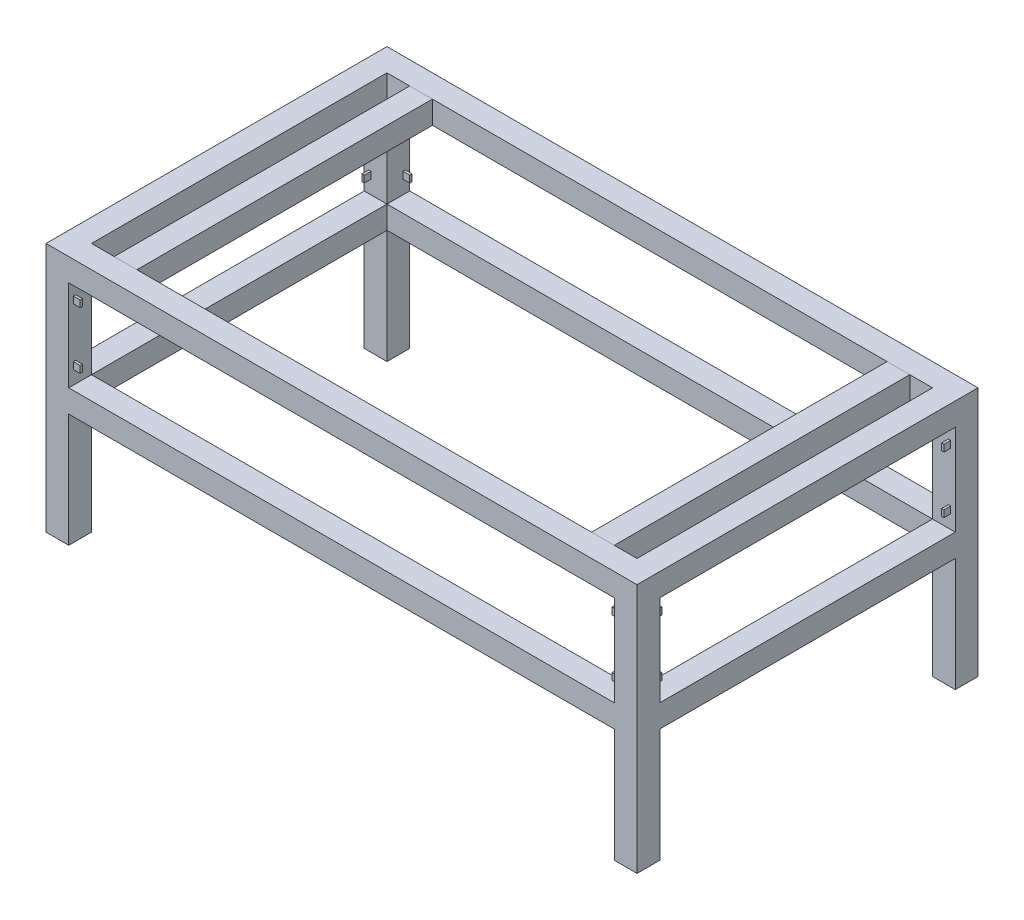
SolidWorks part; units mm, degrees
ref_plane "Plan de face" through (0, 0, 0) normal (0, 0, 1) x (1, 0, 0)
ref_plane "Plan de dessus" through (0, 0, 0) normal (0, 1, 0) x (1, 0, 0)
ref_plane "Plan de droite" through (0, 0, 0) normal (1, 0, 0) x (0, 0, -1)
sketch "Esquisse1" plane through (0, 0, 0) normal (0, 1, 0) x (1, 0, 0)
  line L1 (0, 0) -> (1300, 0)
  line L2 (0, 0) -> (0, 750)
  line L3 (0, 750) -> (1300, 750)
  line L4 (1300, 0) -> (1300, 750)
  line L5 (50, 700) -> (1250, 700)
  line L6 (50, 700) -> (50, 50)
  line L7 (50, 50) -> (1250, 50)
  line L8 (1250, 700) -> (1250, 50)
  dimension "D1" = 1300
  dimension "D2" = 750
  dimension "D3" = 50
  dimension "D4" = 50
  dimension "D5" = 50
  dimension "D6" = 50
extrude "Boss.-Extru.1" add sketch "Esquisse1" against normal blind 550
sketch "Esquisse2" plane through (0, 0, 0) normal (0, 0, 1) x (1, 0, 0)
  line L0 (0, 0) -> (1300, 0) construction
  line L1 (50, -50) -> (1250, -50)
  line L2 (50, -50) -> (50, -250)
  line L3 (50, -250) -> (1250, -250)
  line L4 (1250, -50) -> (1250, -250)
  line L5 (50, -300) -> (1250, -300)
  line L6 (50, -300) -> (50, -550)
  line L7 (50, -550) -> (1250, -550)
  line L8 (1250, -300) -> (1250, -550)
  line L9 (0, -550) -> (1300, -550) construction
  line L10 (1300, -550) -> (1300, 0) construction
  line L11 (0, -550) -> (0, 0) construction
  point P12 (1250, -425)
  dimension "D1" = 50
  dimension "D2" = 50
  dimension "D3" = 200
  dimension "D4" = 0
  dimension "D5" = 50
  dimension "D6" = 50
  dimension "D7" = 50
  dimension "D8" = 50
extrude "Enlèv. mat.-Extru.1" cut sketch "Esquisse2" against normal through all
sketch "Esquisse3" plane through (0, 0, 0) normal (-1, 0, 0) x (0, 0, 1)
  line L0 (-750, -550) -> (0, -550) construction
  line L1 (-700, -50) -> (-50, -50)
  line L2 (-700, -50) -> (-700, -250)
  line L3 (-700, -250) -> (-50, -250)
  line L4 (-50, -50) -> (-50, -250)
  line L5 (-700, -300) -> (-50, -300)
  line L6 (-700, -300) -> (-700, -550)
  line L7 (-700, -550) -> (-50, -550)
  line L8 (-50, -300) -> (-50, -550)
  line L9 (-750, 0) -> (0, 0) construction
  line L10 (0, -550) -> (0, 0) construction
  line L11 (-750, -550) -> (-750, 0) construction
  dimension "D1" = 50
  dimension "D2" = 50
  dimension "D3" = 50
  dimension "D4" = 50
  dimension "D5" = 50
  dimension "D6" = 200
  dimension "D7" = 50
extrude "Enlèv. mat.-Extru.2" cut sketch "Esquisse3" against normal through all
sketch "Esquisse4" plane through (0, 0, 0) normal (0, 1, 0) x (1, 0, 0)
  line L0 (1250, 700) -> (50, 700) construction
  line L1 (100, 700) -> (150, 700)
  line L2 (100, 700) -> (100, 50)
  line L3 (100, 50) -> (150, 50)
  line L4 (150, 700) -> (150, 50)
  line L5 (50, 50) -> (1250, 50) construction
  line L6 (50, 700) -> (50, 50) construction
  line L7 (1150, 700) -> (1200, 700)
  line L8 (1150, 700) -> (1150, 50)
  line L9 (1150, 50) -> (1200, 50)
  line L10 (1200, 700) -> (1200, 50)
  line L11 (1250, 50) -> (1250, 700) construction
  dimension "D1" = 50
  dimension "D2" = 50
  dimension "D3" = 50
  dimension "D4" = 50
extrude "Boss.-Extru.2" add sketch "Esquisse4" against normal blind 50 separate body
sketch "Esquisse5" plane through (1250, 0, 0) normal (-1, 0, 0) x (0, 0, 1)
  line L0 (-750, -250) -> (-750, -50) construction
  line L1 (-750, -80) -> (-735, -80)
  line L2 (-750, -80) -> (-750, -95)
  line L3 (-750, -95) -> (-735, -95)
  line L4 (-735, -80) -> (-735, -95)
  line L5 (-740, -80) -> (-740, -95)
  line L6 (-750, -205) -> (-735, -205)
  line L7 (-750, -205) -> (-750, -220)
  line L8 (-750, -220) -> (-735, -220)
  line L9 (-735, -205) -> (-735, -220)
  line L10 (-740, -205) -> (-740, -220)
  line L11 (-750, -50) -> (-700, -50) construction
  line L12 (-750, -250) -> (-700, -250) construction
  dimension "D1" = 10
  dimension "D2" = 5
  dimension "D3" = 5
  dimension "D4" = 15
  dimension "D5" = 15
  dimension "D6" = 30
  dimension "D7" = 30
extrude "Boss.-Extru.3" add sketch "Esquisse5" along normal blind 15 contours L1 L5 L3 L4 | L6 L10 L8 L9 region at (1250, -87.5, -737.5) region at (1250, -212.5, -737.5)
sketch "Esquisse6" plane through (0, 0, -700) normal (0, 0, 1) x (1, 0, 0)
  line L0 (1300, -50) -> (1300, -250) construction
  line L1 (1300, -80) -> (1285, -80)
  line L2 (1300, -80) -> (1300, -95)
  line L3 (1300, -95) -> (1285, -95)
  line L4 (1285, -80) -> (1285, -95)
  line L5 (1290, -80) -> (1290, -95)
  line L6 (1300, -220) -> (1285, -220)
  line L7 (1300, -220) -> (1300, -205)
  line L8 (1300, -205) -> (1285, -205)
  line L9 (1285, -220) -> (1285, -205)
  line L10 (1290, -205) -> (1290, -220)
  line L11 (1300, -50) -> (1250, -50) construction
  line L12 (1300, -250) -> (1250, -250) construction
  point P18 (1292.5, -220)
  dimension "D1" = 15
  dimension "D2" = 15
  dimension "D3" = 5
  dimension "D4" = 5
  dimension "D5" = 10
  dimension "D6" = 30
  dimension "D7" = 30
extrude "Boss.-Extru.4" add sketch "Esquisse6" along normal blind 15 contours L5 L1 L4 L3 | L10 L8 L9 L6 region at (1287.5, -87.5, -700) region at (1287.5, -212.5, -700)
sketch "Esquisse7" plane through (50, 0, 0) normal (1, 0, 0) x (0, 0, -1)
  line L0 (750, -50) -> (750, -250) construction
  line L1 (750, -80) -> (735, -80)
  line L2 (750, -80) -> (750, -95)
  line L3 (750, -95) -> (735, -95)
  line L4 (735, -80) -> (735, -95)
  line L5 (740, -80) -> (740, -95)
  line L6 (750, -220) -> (735, -220)
  line L7 (750, -220) -> (750, -205)
  line L8 (750, -205) -> (735, -205)
  line L9 (735, -220) -> (735, -205)
  line L10 (740, -205) -> (740, -220)
  line L11 (750, -250) -> (700, -250) construction
  line L12 (750, -50) -> (700, -50) construction
  dimension "D1" = 15
  dimension "D2" = 15
  dimension "D3" = 10
  dimension "D4" = 5
  dimension "D5" = 5
  dimension "D6" = 30
  dimension "D7" = 30
extrude "Boss.-Extru.5" add sketch "Esquisse7" along normal blind 15 contours L5 L1 L4 L3 | L10 L8 L9 L6 region at (50, -87.5, -737.5) region at (50, -212.5, -737.5)
sketch "Esquisse8" plane through (0, 0, -700) normal (0, 0, 1) x (1, 0, 0)
  line L0 (0, -50) -> (0, -250) construction
  line L1 (10, -80) -> (10, -95)
  line L2 (0, -80) -> (15, -80)
  line L3 (0, -80) -> (0, -95)
  line L4 (0, -95) -> (15, -95)
  line L5 (15, -80) -> (15, -95)
  line L6 (0, -205) -> (15, -205)
  line L7 (0, -205) -> (0, -220)
  line L8 (0, -220) -> (15, -220)
  line L9 (15, -205) -> (15, -220)
  line L10 (10, -205) -> (10, -220)
  line L11 (50, -250) -> (0, -250) construction
  line L13 (50, -50) -> (0, -50) construction
  point P16 (7.5, -220)
  dimension "D1" = 15
  dimension "D2" = 5
  dimension "D3" = 10
  dimension "D4" = 30
  dimension "D5" = 5
  dimension "D6" = 10
  dimension "D7" = 15
  dimension "D8" = 30
extrude "Boss.-Extru.6" add sketch "Esquisse8" along normal blind 15 contours L5 L2 L1 L4 | L6 L10 L8 L9 region at (12.5, -87.5, -700) region at (12.5, -212.5, -700)
sketch "Esquisse10" plane through (50, 0, 0) normal (1, 0, 0) x (0, 0, -1)
  line L0 (0, -50) -> (0, -250) construction
  line L1 (0, -80) -> (15, -80)
  line L2 (0, -80) -> (0, -95)
  line L3 (0, -95) -> (15, -95)
  line L4 (15, -80) -> (15, -95)
  line L5 (10, -80) -> (10, -95)
  line L6 (0, -205) -> (15, -205)
  line L7 (0, -205) -> (0, -220)
  line L8 (0, -220) -> (15, -220)
  line L9 (15, -205) -> (15, -220)
  line L10 (10, -205) -> (10, -220)
  line L11 (50, -250) -> (0, -250) construction
  line L12 (50, -50) -> (0, -50) construction
  point P18 (7.5, -80)
  dimension "D1" = 5
  dimension "D2" = 5
  dimension "D3" = 15
  dimension "D4" = 15
  dimension "D5" = 15
  dimension "D6" = 15
  dimension "D7" = 30
  dimension "D8" = 30
extrude "Boss.-Extru.7" add sketch "Esquisse10" along normal blind 15 contours L1 L5 L3 L4 | L6 L10 L8 L9 region at (50, -87.5, -12.5) region at (50, -212.5, -12.5)
sketch "Esquisse12" plane through (0, 0, -50) normal (0, 0, -1) x (-1, 0, 0)
  line L0 (0, -250) -> (0, -50) construction
  line L1 (0, -80) -> (-15, -80)
  line L2 (0, -80) -> (0, -95)
  line L3 (0, -95) -> (-15, -95)
  line L4 (-15, -80) -> (-15, -95)
  line L5 (-10, -80) -> (-10, -95)
  line L6 (0, -205) -> (-15, -205)
  line L7 (0, -205) -> (0, -220)
  line L8 (0, -220) -> (-15, -220)
  line L9 (-15, -205) -> (-15, -220)
  line L10 (-10, -205) -> (-10, -220)
  line L11 (-50, -50) -> (0, -50) construction
  line L12 (-50, -250) -> (0, -250) construction
  point P14 (-15, -87.5)
  dimension "D1" = 15
  dimension "D2" = 15
  dimension "D3" = 15
  dimension "D4" = 15
  dimension "D5" = 5
  dimension "D6" = 5
  dimension "D7" = 30
  dimension "D8" = 30
extrude "Boss.-Extru.8" add sketch "Esquisse12" along normal blind 15 contours L5 L1 L4 L3 | L10 L6 L9 L8 region at (12.5, -87.5, -50) region at (12.5, -212.5, -50)
sketch "Esquisse14" plane through (1250, 0, 0) normal (-1, 0, 0) x (0, 0, 1)
  line L0 (0, -250) -> (0, -50) construction
  line L1 (0, -80) -> (-15, -80)
  line L2 (0, -80) -> (0, -95)
  line L3 (0, -95) -> (-15, -95)
  line L4 (-15, -80) -> (-15, -95)
  line L5 (-10, -80) -> (-10, -95)
  line L6 (0, -205) -> (-15, -205)
  line L7 (0, -205) -> (0, -220)
  line L8 (0, -220) -> (-15, -220)
  line L9 (-15, -205) -> (-15, -220)
  line L10 (-10, -205) -> (-10, -220)
  line L11 (-50, -250) -> (0, -250) construction
  line L12 (-50, -50) -> (0, -50) construction
  point P18 (-15, -87.5)
  dimension "D1" = 15
  dimension "D2" = 5
  dimension "D3" = 15
  dimension "D4" = 30
  dimension "D5" = 30
  dimension "D6" = 5
  dimension "D7" = 15
  dimension "D8" = 15
extrude "Boss.-Extru.9" add sketch "Esquisse14" along normal blind 15 contours L5 L1 L4 L3 | L10 L6 L9 L8 region at (1250, -87.5, -12.5) region at (1250, -212.5, -12.5)
sketch "Esquisse15" plane through (0, 0, -50) normal (0, 0, -1) x (-1, 0, 0)
  line L0 (-1300, -250) -> (-1300, -50) construction
  line L1 (-1300, -80) -> (-1285, -80)
  line L2 (-1300, -80) -> (-1300, -95)
  line L3 (-1300, -95) -> (-1285, -95)
  line L4 (-1285, -80) -> (-1285, -95)
  line L5 (-1290, -80) -> (-1290, -95)
  line L6 (-1300, -205) -> (-1285, -205)
  line L7 (-1300, -205) -> (-1300, -220)
  line L8 (-1300, -220) -> (-1285, -220)
  line L9 (-1285, -205) -> (-1285, -220)
  line L10 (-1290, -205) -> (-1290, -220)
  line L11 (-1300, -50) -> (-1250, -50) construction
  line L12 (-1300, -250) -> (-1250, -250) construction
  point P14 (-1285, -212.5)
  point P15 (-1300, -212.5)
  dimension "D1" = 15
  dimension "D2" = 15
  dimension "D3" = 15
  dimension "D4" = 5
  dimension "D5" = 15
  dimension "D6" = 30
  dimension "D7" = 30
extrude "Boss.-Extru.10" add sketch "Esquisse15" along normal blind 15 contours L6 L10 L8 L9 | L1 L5 L3 L4 region at (1287.5, -87.5, -50) region at (1287.5, -212.5, -50)
